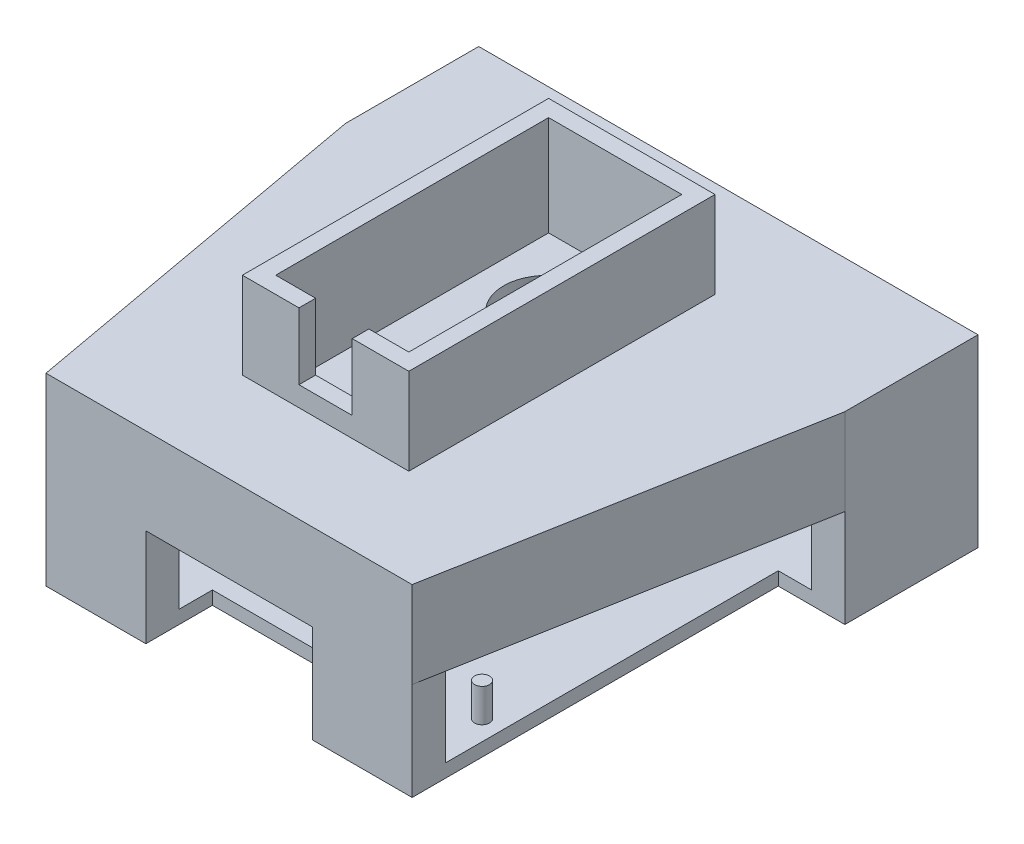
SolidWorks part; units mm, degrees
ref_plane "Front Plane" through (0, 0, 0) normal (0, 0, 1) x (1, 0, 0)
ref_plane "Top Plane" through (0, 0, 0) normal (0, 1, 0) x (1, 0, 0)
ref_plane "Right Plane" through (0, 0, 0) normal (1, 0, 0) x (0, 0, -1)
sketch "Sketch1" plane through (0, 0, 0) normal (0, 1, 0) x (1, 0, 0)
  line L1 (0, 0) -> (55, 0)
  line L2 (0, 0) -> (0, 65)
  line L3 (0, 65) -> (55, 65)
  line L4 (55, 0) -> (55, 65)
  dimension "D1" = 55
  dimension "D2" = 65
extrude "Base" add sketch "Sketch1" along normal blind 2
sketch "Sketch2" plane through (0, 2, 0) normal (0, 1, 0) x (1, 0, 0)
  line L0 (0, 0) -> (55, 0) construction
  line L2 (55, 65) -> (0, 65) construction
  circle A0 centre (3, 3.5) radius 1.125
  circle A1 centre (52, 3.5) radius 1.125
  circle A2 centre (3, 61.5) radius 1.125
  circle A3 centre (52, 61.5) radius 1.125
  point P12 (27.5, 0)
  dimension "D1" = 2.25
  dimension "D2" = 24.5
  dimension "D3" = 24.5
  dimension "D4" = 58
  dimension "D5" = 3.5
extrude "PiMountPegs" add sketch "Sketch2" along normal blind 5
sketch "Sketch3" plane through (0, 0, 0) normal (-1, 0, 0) x (0, 0, 1)
  line L0 (-65, 0) -> (0, 0) construction
  line L1 (-65, 2) -> (-45, 2)
  line L2 (-65, 2) -> (-65, 0)
  line L3 (-65, 0) -> (-45, 0)
  line L4 (-45, 2) -> (-45, 0)
  dimension "D1" = 20
extrude "ServoPlateLegExt-1" add sketch "Sketch3" along normal blind 10
sketch "Sketch4" plane through (55, 0, 0) normal (1, 0, 0) x (0, 0, -1)
  line L0 (0, 0) -> (65, 0) construction
  line L1 (65, 2) -> (45, 2)
  line L2 (65, 2) -> (65, 0)
  line L3 (65, 0) -> (45, 0)
  line L4 (45, 2) -> (45, 0)
  dimension "D1" = 20
extrude "ServoPlateLegExt-2" add sketch "Sketch4" along normal blind 10
sketch "Sketch5" plane through (0, 0, 0) normal (0, 0, 1) x (1, 0, 0)
  line L0 (0, 0) -> (55, 0) construction
  line L1 (0, 2) -> (15, 2)
  line L2 (0, 2) -> (0, 0)
  line L3 (0, 0) -> (15, 0)
  line L4 (15, 2) -> (15, 0)
  line L6 (55, 2) -> (40, 2)
  line L7 (55, 2) -> (55, 0)
  line L8 (55, 0) -> (40, 0)
  line L9 (40, 2) -> (40, 0)
  dimension "D1" = 15
  dimension "D2" = 15
extrude "ServoPlateLegExt-3" add sketch "Sketch5" along normal blind 10
sketch "Sketch6" plane through (0, 2, 0) normal (0, 1, 0) x (1, 0, 0)
  line L0 (-10, 45) -> (0, 45) construction
  line L1 (-10, 65) -> (-5, 65)
  line L2 (-10, 65) -> (-10, 45)
  line L3 (-10, 45) -> (-5, 45)
  line L4 (-5, 65) -> (-5, 45)
  line L5 (15, -10) -> (15, 0) construction
  line L6 (0, -10) -> (15, -10)
  line L7 (0, -10) -> (0, -5)
  line L8 (0, -5) -> (15, -5)
  line L9 (15, -10) -> (15, -5)
  line L10 (40, -10) -> (40, 0) construction
  line L11 (55, -10) -> (40, -10)
  line L12 (55, -10) -> (55, -5)
  line L13 (55, -5) -> (40, -5)
  line L14 (40, -10) -> (40, -5)
  line L15 (65, 45) -> (55, 45) construction
  line L16 (65, 65) -> (60, 65)
  line L17 (65, 65) -> (65, 45)
  line L18 (65, 45) -> (60, 45)
  line L19 (60, 65) -> (60, 45)
extrude "ServoLegs" add sketch "Sketch6" along normal blind 12.7
sketch "Sketch11" plane through (0, 14.7, 0) normal (0, 1, 0) x (1, 0, 0)
  line L0 (55, -10) -> (65, 45)
  line L1 (65, 45) -> (65, 65)
  line L2 (65, 65) -> (-10, 65)
  line L3 (-10, 65) -> (-10, 45)
  line L4 (-10, 45) -> (0, -10)
  line L5 (0, -10) -> (55, -10)
extrude "ServoPlate" add sketch "Sketch11" along normal blind 13
sketch "Sketch12" plane through (0, 27.7, 0) normal (0, 1, 0) x (1, 0, 0)
  line L0 (65, 65) -> (-10, 65) construction
  line L1 (17.5, 7) -> (37.5, 7)
  line L2 (17.5, 7) -> (17.5, 48)
  line L3 (17.5, 48) -> (37.5, 48)
  line L4 (37.5, 7) -> (37.5, 48)
  line L5 (-10, 65) -> (-10, -10) construction
  point P4 (27.5, 48)
  point P7 (27.5, 65)
  point P11 (17.5, 27.5)
  point P12 (-10, 27.5)
  dimension "D1" = 41
  dimension "D2" = 20
extrude "ServoSeat" cut sketch "Sketch12" against normal blind 2
sketch "Sketch13" plane through (0, 25.7, 0) normal (0, 1, 0) x (1, 0, 0)
  line L1 (37.5, 48) -> (17.5, 48) construction
  circle A0 centre (27.5, 37.75) radius 1.5
  point P6 (27.5, 48)
  dimension "D1" = 3
  dimension "D2" = 10.25
extrude "ServoScrewHole-1" cut sketch "Sketch13" against normal up to surface (11 mm away) up to face at (27.5, 14.7, -17.8571)
sketch "Sketch14" plane through (0, 25.7, 0) normal (0, 1, 0) x (1, 0, 0)
  circle A0 centre (27.5, 37.75) radius 6.5
  circle A1 centre (27.5, 37.75) radius 1.5 construction
  dimension "D1" = 13
extrude "ServoAxleHole" cut sketch "Sketch14" against normal blind 7
sketch "Sketch17" plane through (0, 27.7, 0) normal (0, 1, 0) x (1, 0, 0)
  line L1 (17.5, 48) -> (37.5, 48)
  line L2 (17.5, 48) -> (17.5, 7)
  line L3 (17.5, 7) -> (37.5, 7)
  line L4 (37.5, 48) -> (37.5, 7)
  line L5 (15, 50.5) -> (40, 50.5)
  line L6 (15, 50.5) -> (15, 4.5)
  line L7 (15, 4.5) -> (40, 4.5)
  line L8 (40, 50.5) -> (40, 4.5)
  dimension "D1" = 2.5
  dimension "D2" = 2.5
  dimension "D3" = 2.5
  dimension "D4" = 2.5
extrude "Extra-Inset" add sketch "Sketch17" along normal blind 3
sketch "Sketch18" plane through (0, 30.7, 0) normal (0, 1, 0) x (1, 0, 0)
  line L0 (17.5, 48) -> (17.5, 7)
  line L1 (17.5, 7) -> (23.5, 7)
  line L2 (17.5, 7) -> (37.5, 7) construction
  line L3 (23.5, 7) -> (23.5, 4.5)
  line L4 (15, 4.5) -> (40, 4.5) construction
  line L5 (15, 4.5) -> (23.5, 4.5)
  line L6 (31.5, 4.5) -> (31.5, 7)
  line L7 (31.5, 7) -> (37.5, 7)
  line L8 (37.5, 7) -> (37.5, 48)
  line L9 (31.5, 4.5) -> (40, 4.5)
  line L10 (40, 50.5) -> (15, 50.5)
  line L11 (40, 50.5) -> (40, 4.5)
  line L13 (15, 50.5) -> (15, 4.5)
  line L18 (17.5, 7) -> (37.5, 7)
  line L19 (17.5, 48) -> (17.5, 7)
  line L20 (37.5, 48) -> (17.5, 48)
  line L21 (37.5, 7) -> (37.5, 48)
  line L24 (37.5, 48) -> (17.5, 48)
  point P4 (27.5, 4.5)
  dimension "D1" = 8
  dimension "D2" = 4
  dimension "D3" = 0
extrude "StabilizingWalls" add sketch "Sketch18" along normal blind 10
equation "\"PlateLegExtent\"= 10mm"
equation "\"D1@ServoPlateLegExt-1\" = \"PlateLegExtent\""
equation "\"D1@ServoPlateLegExt-3\" = \"PlateLegExtent\""
equation "\"D1@ServoPlateLegExt-2\" = \"PlateLegExtent\""
equation "\"PlateLegHeight\"= 1in"
equation "\"D1@ServoLegs\"=\"PlateLegHeight\"/2"
equation "\"PlateThickness\"=6"
